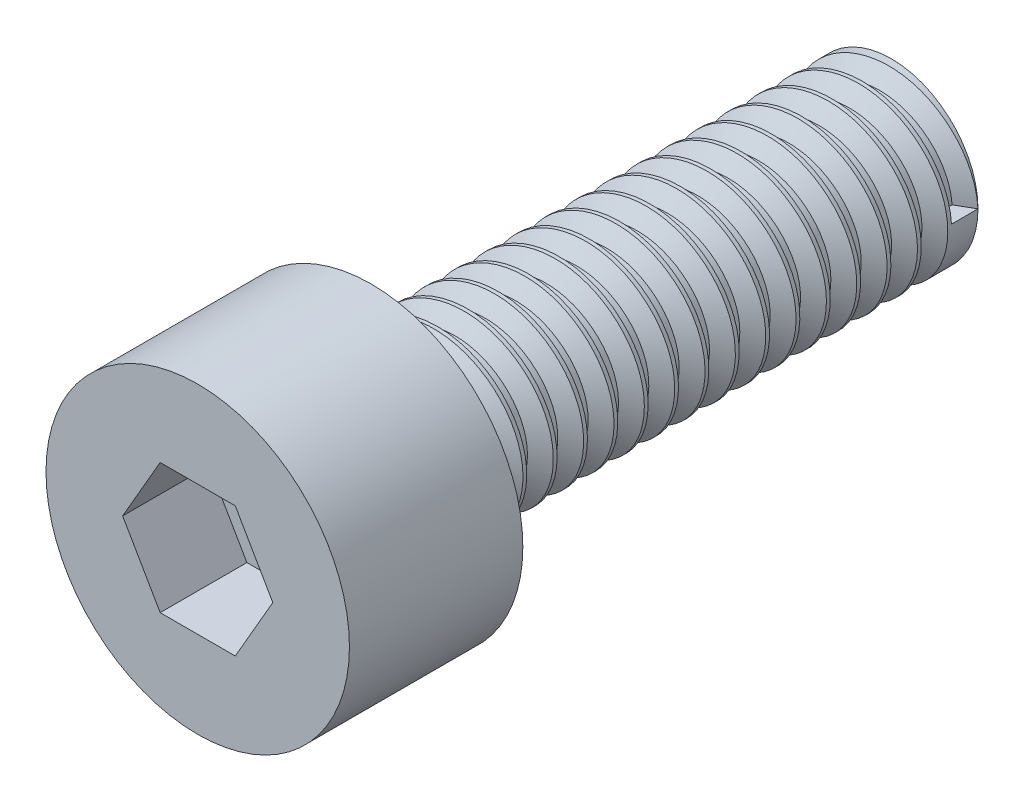
SolidWorks part; units mm, degrees
other "标注1"
sketch "草图4" plane through (3.5, -3.5, -0.1132) normal (1, 0, 0) x (0, 0, -1)
ref_plane "前视基准面" through (0, 0, 0) normal (0, 0, 1) x (1, 0, 0)
ref_plane "上视基准面" through (0, 0, 0) normal (0, 1, 0) x (1, 0, 0)
ref_plane "右视基准面" through (0, 0, 0) normal (1, 0, 0) x (0, 0, -1)
sketch "草图1" plane through (0, 0, 0) normal (0, 0, 1) x (1, 0, 0)
  circle A0 centre (0, 0) radius 2
  dimension "diameter" = 4
extrude "螺杆_直径3_长度10" add sketch "草图1" along normal blind 12
thread "真实螺纹_M4x0.7_右旋_长12" pitch 0.7 method cut profile "螺纹线轮廓1" start angle 0, offset 0, length 12, pitch 0.7, diameter 4
ref_plane "基准面1" through (2, 0, 0) normal (0, -1, 0) x (1, 0, 0)
sketch "螺纹线轮廓1" plane through (2, 0, 0) normal (0, -1, 0) x (1, 0, 0)
  line L0 (0, 0) -> (0, 0.7) construction
  line L11 (0, 0) -> (0, 0.6125)
  line L12 (0, 0.6125) -> (-0.3789, 0.3937)
  line L13 (-0.3789, 0.3937) -> (-0.3789, 0.2187)
  line L15 (-0.3789, 0.2187) -> (0, 0)
  line L17 (-0.3789, 0.3062) -> (0, 0.3062) construction
  point P2 (0, 0)
  dimension "Pitch" = 0.7
  dimension "Profile_Angle" = 60
  dimension "Profile_Land" = 0.175
  dimension "Profile_Height" = 0.3789
sketch "草图2" plane through (0, 0, 12) normal (0, 0, 1) x (1, 0, 0)
  circle A0 centre (0, 0) radius 3.5
  dimension "diameter" = 7
extrude "杯头_直径5.5_厚度3" add sketch "草图2" along normal blind 4
sketch "草图3" plane through (0, 0, 16) normal (0, 0, 1) x (1, 0, 0)
  line L0 (1.7321, 0) -> (0.866, 1.5)
  line L1 (0.866, 1.5) -> (-0.866, 1.5)
  line L2 (-0.866, 1.5) -> (-1.7321, 0)
  line L3 (-1.7321, 0) -> (-0.866, -1.5)
  line L4 (-0.866, -1.5) -> (0.866, -1.5)
  line L5 (0.866, -1.5) -> (1.7321, 0)
  dimension "x0" = 1.7321
  dimension "x1" = 0.866
  dimension "x2" = 0.866
  dimension "x3" = 1.7321
  dimension "x4" = 0.866
  dimension "x5" = 0.866
  dimension "y1" = 1.5
  dimension "y4" = 1.5
extrude "内六角_对边2.5_深1.5" cut sketch "草图3" against normal blind 2
